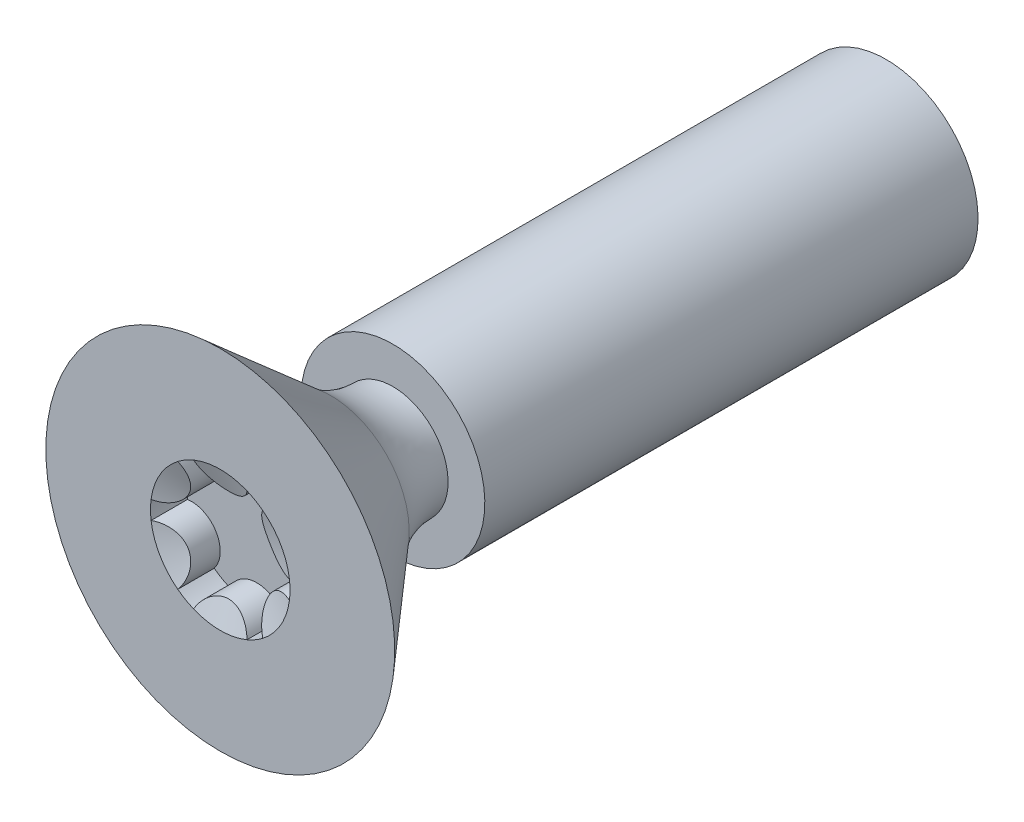
SolidWorks part; units mm, degrees
material "Plain Carbon Steel"
ref_plane "Front Plane" through (0, 0, 0) normal (0, 0, 1) x (1, 0, 0)
ref_plane "Top Plane" through (0, 0, 0) normal (0, 1, 0) x (1, 0, 0)
ref_plane "Right Plane" through (0, 0, 0) normal (1, 0, 0) x (0, 0, -1)
sketch "Sketch1" plane through (0, 0, 0) normal (1, 0, 0) x (0, 0, -1)
  line L0 (-6.35, 0) -> (6.35, 0) construction
  line L1 (6.35, 0) -> (6.35, 1.7526) construction
  line L2 (6.35, 1.7526) -> (-4.2418, 1.7526) construction
  line L4 (-6.35, 3.3274) -> (-6.35, 0) construction
  line L5 (6.35, -1.7526) -> (6.35, 1.7526) construction
  line L6 (6.2664, 1.8973) -> (6.9349, 0.7396) construction
  line L7 (6.9349, 0.7396) -> (7.6033, 1.8973) construction
  line L8 (7.6033, 1.8973) -> (6.2664, 1.8973) construction
  line L9 (6.9349, 0.7396) -> (6.9349, 0.8843) construction
  line L10 (6.9349, 1.8973) -> (6.9349, 1.7526) construction
  line L11 (7.5197, 1.7526) -> (6.35, 1.7526) construction
  line L12 (6.9349, 1.825) -> (7.5615, 1.825) construction
  line L13 (6.9349, 1.825) -> (6.3082, 1.825) construction
  line L14 (6.8513, 0.8843) -> (7.0184, 0.8843) construction
  line L15 (-6.35, 3.3274) -> (-4.2418, 0.9022) construction
  line L16 (4.3447, 1.7526) -> (4.3447, 0) construction
  line L17 (4.3447, 1.7526) -> (5.0132, 1.6347) construction
  line L18 (5.0132, 1.6347) -> (5.6816, 1.5169) construction
  line L19 (5.6816, 1.5169) -> (6.35, 1.399) construction
  line L20 (-6.35, 0.9022) -> (-4.2418, 0.9022) construction
  line L21 (-4.2418, 1.7526) -> (-4.2418, 0.9022) construction
  line L22 (-4.3716, 1.0516) -> (4.3447, 1.0516) construction
  line L23 (-6.35, 3.3274) -> (-3.7319, 1.0516) construction
  line L24 (6.7547, 1.0516) -> (7.115, 1.0516) construction
  line L25 (-3.5734, 1.7526) -> (-4.2744, 1.0516) construction
  line L26 (-6.35, 2.1336) -> (-3.9624, 0) construction
  line L27 (-6.35, 0.3683) -> (-4.3745, 0.3683) construction
  line L28 (-3.7319, 1.0516) -> (-2.5223, 0) construction
  line L30 (-3.0564, 0) -> (-3.0564, 1.7526) construction
  line L31 (-2.0538, 0) -> (-2.0538, 1.7526) construction
  arc A1 (-4.4568, 1.1496) -> (-4.2418, 1.0516) centre (-4.2418, 1.3365) ccw construction
  arc A2 (-4.2418, 1.4948) -> (-3.0564, 1.0516) centre (-3.0564, 2.8584) ccw construction
  point P0 (2.3395, 1.7526)
  point P4 (0, 0)
  point P10 (6.35, 0)
  point P41 (-4.0221, 1.3038)
  point P45 (-6.35, 1.331)
  point P55 (-5.7175, 0.9022)
  dimension "Length" = 12.7
  dimension "Screw OD" = 3.5052
  dimension "Head DIa" = 6.6548
  dimension "Pitch" = 1.3368
  dimension "D2" = 0.1671
  dimension "D3" = 41
  dimension "D4" = 10
  dimension "D5" = 1.3368
  dimension "Head Ht" = 2.1082
  dimension "D6" = 0.701
  dimension "D1" = 4.0105
  dimension "D7" = 49
  dimension "D8" = 45
  dimension "D9" = 0.6684
  dimension "D10" = 2.6619
  dimension "Recess Wd" = 0.7366
  dimension "Recess Dia" = 4.2672
  dimension "Recess Dp" = 2.3876
  dimension "D11" = 1.0026
  dimension "D12" = 0.6325
sketch "Sketch2" plane through (0, 0, 0) normal (0, 0, 1) x (1, 0, 0)
  line L0 (0, 0) -> (1.5178, -0.8763) construction
  line L1 (0, 0) -> (-1.5178, -0.8763) construction
  line L2 (0, 0.7396) -> (0, 1.8973) construction
  line L5 (0, 3.3274) -> (0, 0) construction
  line L12 (0, 0) -> (0.6655, 1.1526) construction
  line L13 (0, 0) -> (-0.6655, 1.1526) construction
  line L14 (0, 0) -> (-0.5093, 1.2296) construction
  line L15 (0, 0) -> (0.5093, 1.2296) construction
  line L17 (0, -1.7526) -> (0, 1.7526) construction
  circle A7 centre (0, 0) radius 1.7526 construction
  circle A9 centre (0, 0) radius 1.331 construction
  arc A10 (-0.5093, 1.2296) -> (0.5093, 1.2296) centre (0, 1.4406) ccw construction
  arc A11 (-0.3547, 1.6562) -> (0.3547, 1.6562) centre (0, 1.0516) cw construction
  arc A12 (-1.6117, -0.521) -> (-1.257, -1.1353) centre (-0.9107, -0.5258) ccw construction
  arc A13 (1.6117, -0.521) -> (1.257, -1.1353) centre (0.9107, -0.5258) cw construction
  arc A14 (-1.6117, -0.521) -> (-0.3547, 1.6562) centre (0.9327, -0.5385) cw construction
  arc A15 (0.3547, 1.6562) -> (1.6117, -0.521) centre (-0.9327, -0.5385) cw construction
  arc A16 (1.257, -1.1353) -> (-1.257, -1.1353) centre (0, 1.077) cw construction
  circle A17 centre (0, 0) radius 1.0516 construction
  point P0 (0, 3.3274)
  point P17 (1.5178, -0.8763)
  point P19 (-1.5178, -0.8763)
  point P21 (0, 1.0516)
  point P22 (1.5178, -0.8763)
  point P25 (0, -1.4675)
  point P26 (-1.5178, -0.8763)
  point P29 (0, 1.7526)
  point P66 (-0.9107, -0.5258)
  dimension "D1" = 0.701
  dimension "D2" = 120
  dimension "D3" = 120
  dimension "D6" = 7.5
  dimension "D7" = 7.5
  dimension "D8" = 30
  dimension "D9" = 30
  dimension "D4" = 0.0254
sketch "Sketch3" plane through (0, 0, 0) normal (1, 0, 0) x (0, 0, -1)
  line L0 (6.35, 0) -> (6.35, 1.7526) construction
  line L1 (-6.35, 0) -> (6.35, 0) construction
  line L2 (6.35, 1.7526) -> (-4.2418, 1.7526) construction
  line L3 (-3.0564, 1.7526) -> (-3.0564, 1.0516)
  line L4 (-6.35, 3.3274) -> (-6.35, 0) construction
  line L5 (6.35, 0) -> (6.35, 1.7526)
  line L6 (-6.35, 0) -> (6.35, 0)
  line L7 (6.35, 1.7526) -> (-3.0564, 1.7526)
  line L9 (-6.35, 3.3274) -> (-6.35, 0)
  line L15 (-6.35, 3.3274) -> (-3.7319, 1.0516) construction
  line L17 (-6.35, 3.3274) -> (-4.2418, 1.4948)
  arc A0 (-4.2418, 1.4948) -> (-3.0564, 1.0516) centre (-3.0564, 2.8584) ccw construction
  arc A1 (-4.2418, 1.4948) -> (-3.0564, 1.0516) centre (-3.0564, 2.8584) ccw
revolve "Revolve1" add sketch "Sketch3" angle 360 about L0
ref_plane "Plane1" through (0, 0, 6.35) normal (0, 0, 1) x (1, 0, 0)
ref_plane "Plane5" through (0, 0, -4.3447) normal (0, 0, 1) x (1, 0, 0)
ref_plane "Plane6" through (0, 0, 3.0564) normal (0, 0, 1) x (1, 0, 0)
ref_plane "Plane7" through (0, 0, 2.0538) normal (0, 0, 1) x (1, 0, 0)
sketch "Sketch21" plane through (0, 0, 6.35) normal (0, 0, 1) x (1, 0, 0)
  line L0 (0, 0) -> (-0.6655, 1.1526) construction
  line L3 (0, 0) -> (0.6655, 1.1526) construction
  line L4 (0, 0) -> (-0.6655, 1.1526)
  line L7 (0, 0) -> (0.6655, 1.1526)
  circle A0 centre (0, 0) radius 1.331 construction
  arc A1 (-0.5093, 1.2296) -> (0.5093, 1.2296) centre (0, 1.4406) ccw construction
  arc A2 (0.6655, 1.1526) -> (0.5093, 1.2296) centre (0, 0) ccw
  arc A3 (-0.5093, 1.2296) -> (0.5093, 1.2296) centre (0, 1.4406) ccw
  arc A4 (-0.5093, 1.2296) -> (-0.6655, 1.1526) centre (0, 0) ccw
extrude "Cut-Extrude14" cut sketch "Sketch21" against normal blind 0.6957
pattern_circular "CirPattern1" count 6 over 360 about axis through (0, 0, 6.35) along (0, 0, -1) of "Cut-Extrude14"
sketch "Sketch22" plane through (0, 0, 6.35) normal (0, 0, 1) x (1, 0, 0)
  circle A0 centre (0, 0) radius 1.331 construction
  circle A1 centre (0, 0) radius 1.331
extrude "Cut-Extrude15" cut sketch "Sketch22" against normal up to vertex (0.6325 mm away) draft 70 up to point (0, 0.9022, 5.7175)
sketch "Sketch20" plane through (0, 0, 0) normal (1, 0, 0) x (0, 0, -1)
  line L0 (6.35, -1.7526) -> (6.35, 1.7526) construction
  point P0 (4.3447, -1.4675)
  dimension "D1" = 2.0053
sketch "Sketch24" plane through (0, 0, 6.35) normal (0, 0, 1) x (1, 0, 0)
  circle A0 centre (0, 0) radius 3.3274
  point P0 (0.8102, -1.0559)
ref_axis "Center Axis 1" through (0, 0, 6.35) along (0, 0, -1)
ref_plane "Contact Plane 1" through (0, 0, -6.35) normal (0, 0, -1) x (-1, 0, 0)
ref_plane "Contact Plane 2" through (0, 0, 4.2418) normal (0, 0, 1) x (1, 0, 0)
sketch "Sketch8" [suppressed] plane through (0, 0, -6.35) normal (0, 0, -1) x (-1, 0, 0)
  line L0 (0, -1.7526) -> (0, 1.7526) construction
  circle A0 centre (0, 0) radius 1.7526
  point P0 (0, 1.7526)
curve "Helix/Spiral1" [suppressed] pitch 1.3368 height 11.9286 turns 8.923
split "Split1" [suppressed] bodies to split 147
sketch "Sketch9" [suppressed] plane through (0, 0, 0) normal (1, 0, 0) x (0, 0, -1)
  line L0 (6.3082, 1.825) -> (6.7547, 1.0516)
  line L2 (7.115, 1.0516) -> (7.5615, 1.825)
  line L3 (6.3082, 1.825) -> (7.5615, 1.825)
  line L5 (6.7547, 1.0516) -> (7.115, 1.0516)
sweep "Cut-Sweep1" [suppressed] cut profiles "Sketch9" path "Helix/Spiral1"
sketch "Sketch11" [suppressed] plane through (0, 0, 3.0564) normal (0, 0, 1) x (1, 0, 0)
  arc A0 (1.257, -1.1353) -> (1.6117, -0.521) centre (0.9107, -0.5258) ccw construction
  arc A1 (-1.257, -1.1353) -> (1.257, -1.1353) centre (0, 1.077) ccw construction
  arc A2 (-1.6117, -0.521) -> (-1.257, -1.1353) centre (-0.9107, -0.5258) ccw construction
  arc A3 (-0.3547, 1.6562) -> (-1.6117, -0.521) centre (0.9327, -0.5385) ccw construction
  arc A4 (0.3547, 1.6562) -> (-0.3547, 1.6562) centre (0, 1.0516) ccw construction
  arc A5 (1.6117, -0.521) -> (0.3547, 1.6562) centre (-0.9327, -0.5385) ccw construction
  arc A6 (1.257, -1.1353) -> (1.6117, -0.521) centre (0.9107, -0.5258) ccw
  arc A7 (-1.257, -1.1353) -> (1.257, -1.1353) centre (0, 1.077) ccw
  arc A8 (-1.6117, -0.521) -> (-1.257, -1.1353) centre (-0.9107, -0.5258) ccw
  arc A9 (-0.3547, 1.6562) -> (-1.6117, -0.521) centre (0.9327, -0.5385) ccw
  arc A10 (0.3547, 1.6562) -> (-0.3547, 1.6562) centre (0, 1.0516) ccw
  arc A11 (1.6117, -0.521) -> (0.3547, 1.6562) centre (-0.9327, -0.5385) ccw
extrude "Cut-Extrude3" [suppressed] cut sketch "Sketch11" against normal through all flip side to cut
sketch "Sketch18" [suppressed] plane through (0, 0, 2.0538) normal (0, 0, 1) x (1, 0, 0)
  circle A0 centre (0, 0) radius 1.7526
  point P0 (0, 1.7526)
extrude "Cut-Extrude13" [suppressed] cut sketch "Sketch18" along normal through all draft 35.5 flip side to cut draft outward yes
sketch "Sketch12" [suppressed] plane through (0, 0, -4.3447) normal (0, 0, 1) x (1, 0, 0)
  arc A0 (-1.6117, -0.521) -> (-1.257, -1.1353) centre (-0.9107, -0.5258) ccw construction
  arc A1 (-1.257, -1.1353) -> (1.257, -1.1353) centre (0, 1.077) ccw construction
  arc A2 (1.257, -1.1353) -> (1.6117, -0.521) centre (0.9107, -0.5258) ccw construction
  arc A3 (1.6117, -0.521) -> (0.3547, 1.6562) centre (-0.9327, -0.5385) ccw construction
  arc A4 (0.3547, 1.6562) -> (-0.3547, 1.6562) centre (0, 1.0516) ccw construction
  arc A5 (-0.3547, 1.6562) -> (-1.6117, -0.521) centre (0.9327, -0.5385) ccw construction
  arc A6 (-1.6117, -0.521) -> (-1.257, -1.1353) centre (-0.9107, -0.5258) ccw
  arc A7 (-1.257, -1.1353) -> (1.257, -1.1353) centre (0, 1.077) ccw
  arc A8 (1.257, -1.1353) -> (1.6117, -0.521) centre (0.9107, -0.5258) ccw
  arc A9 (1.6117, -0.521) -> (0.3547, 1.6562) centre (-0.9327, -0.5385) ccw
  arc A10 (0.3547, 1.6562) -> (-0.3547, 1.6562) centre (0, 1.0516) ccw
  arc A11 (-0.3547, 1.6562) -> (-1.6117, -0.521) centre (0.9327, -0.5385) ccw
extrude "Cut-Extrude4" [suppressed] cut sketch "Sketch12" against normal through all draft 7 flip side to cut draft outward yes
sketch "Sketch15" [suppressed] plane through (0, 0, 0) normal (1, 0, 0) x (0, 0, -1)
  line L14 (-1.9881, 0) -> (-3.0564, 0)
  line L17 (-3.0564, 0) -> (-3.0564, 1.0516)
  line L18 (-3.0564, 1.0516) -> (-1.9881, 1.0516)
  line L19 (-4.3716, 1.0516) -> (4.3447, 1.0516) construction
  line L20 (-1.9881, 1.0516) -> (-1.9881, 0)
  point P3 (-2.5223, 0)
revolve "Revolve3" [suppressed] add sketch "Sketch15" angle 360 about L0
equation "\"D2@Sketch1\"=\"Pitch@Sketch1\"/8"
equation "\"D5@Sketch1\"=\"Pitch@Sketch1\""
equation "\"D6@Sketch1\"=\"Screw OD@Sketch1\"*.2"
equation "\"D9@Sketch1\"=\"Pitch@Sketch1\"*.5"
equation "\"D1@Sketch1\"=\"Pitch@Sketch1\"*3"
equation "\"D1@Sketch2\"=\"Screw OD@Sketch1\"*.2"
equation "\"D4@Helix/Spiral1\"=\"Pitch@Sketch1\""
equation "\"D3@Helix/Spiral1\"=\"Length@Sketch1\"-\"Head Ht@Sketch1\"+\"Pitch@Sketch1\""
equation "\"D10@Sketch1\"=\"Head DIa@Sketch1\"*.4"
equation "\"D11@Sketch1\"=\"Pitch@Sketch1\"*.75"
equation "\"D1@Sketch20\"=\"Pitch@Sketch1\"*1.5"
equation "\"D1@Cut-Extrude14\"=\"Head Ht@Sketch1\"*.33"
equation "\"D12@Sketch1\"=\"Head Ht@Sketch1\"*.3"
